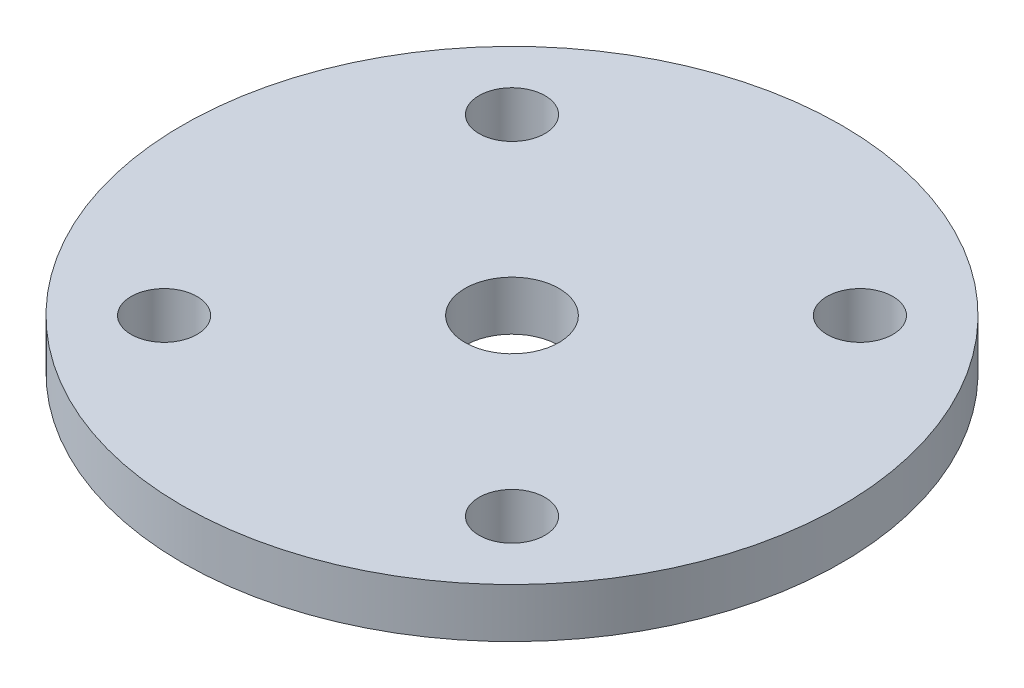
SolidWorks part; units mm, degrees
ref_plane "Plano frontal" through (0, 0, 0) normal (0, 0, 1) x (1, 0, 0)
ref_plane "Plano superior" through (0, 0, 0) normal (0, 1, 0) x (1, 0, 0)
ref_plane "Plano direito" through (0, 0, 0) normal (1, 0, 0) x (0, 0, -1)
ref_plane "Plano1" through (0, -3, 0) normal (0, -1, 0) x (1, 0, 0)
sketch "Esboço1" plane through (0, -3, 0) normal (0, -1, 0) x (1, 0, 0)
  circle A0 centre (0, 0) radius 2.85
  circle A1 centre (10.5571, 10.5571) radius 2
  circle A2 centre (10.5571, -10.5571) radius 2
  circle A3 centre (-10.5571, -10.5571) radius 2
  circle A4 centre (-10.5571, 10.5571) radius 2
  circle A5 centre (0, 0) radius 20
  point P4 (-6.7243, -8.4321)
  point P5 (0, 0)
  point P6 (0, 0)
  point P14 (0, 0)
  dimension "D1" = 4
  dimension "D2" = 40
  dimension "D3" = 5.7
  dimension "D4" = 14.93
  dimension "D5" = 4
extrude "Ressalto-extrusão1" add sketch "Esboço1" against normal blind 3
